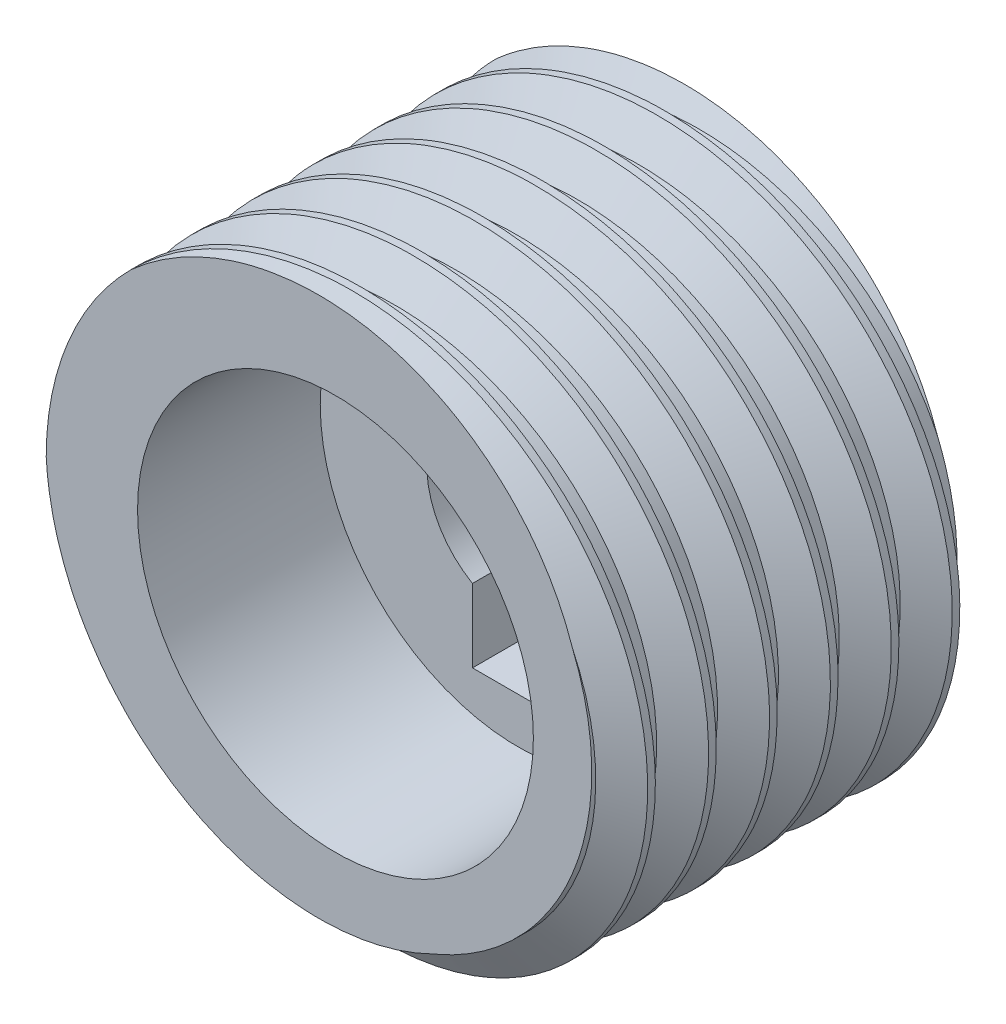
SolidWorks part; units mm, degrees
ref_plane "Front Plane" through (0, 0, 0) normal (0, 0, 1) x (1, 0, 0)
ref_plane "Top Plane" through (0, 0, 0) normal (0, 1, 0) x (1, 0, 0)
ref_plane "Right Plane" through (0, 0, 0) normal (1, 0, 0) x (0, 0, -1)
sketch "Sketch2" plane through (0, 0, 0) normal (0, 0, 1) x (1, 0, 0)
  circle A0 centre (0, 0) radius 4.75
  dimension "D1" = 9.5
extrude "Boss-Extrude1" add sketch "Sketch2" against normal blind 6
sketch "Sketch5" plane through (0, 0, 0) normal (0, 0, 1) x (1, 0, 0)
  circle A0 centre (0, 0) radius 3.25
  dimension "D1" = 6.5
extrude "Cut-Extrude1" cut sketch "Sketch5" against normal blind 3
thread "Thread1" pitch 1 method cut trim with start face yes profile "Thread Profile1" start angle 0, offset 1, length 0, pitch 1, diameter 9.5
ref_plane "Plane1" through (-4.75, 0, 1) normal (0, -1, 0) x (-1, 0, 0)
sketch "Thread Profile1" plane through (-4.75, 0, 1) normal (0, -1, 0) x (-1, 0, 0)
  line L0 (0, 0) -> (0, 1) construction
  line L11 (0, 0) -> (0, 0.875)
  line L12 (0, 0.875) -> (-0.5413, 0.5625)
  line L13 (-0.5413, 0.5625) -> (-0.5413, 0.3125)
  line L15 (-0.5413, 0.3125) -> (0, 0)
  line L17 (-0.5413, 0.4375) -> (0, 0.4375) construction
  point P2 (0, 0)
  dimension "Pitch" = 1
  dimension "Profile_Angle" = 60
  dimension "Profile_Land" = 0.25
  dimension "Profile_Height" = 0.5413
sketch "Sketch11" plane through (0, 0, -3) normal (0, 0, 1) x (1, 0, 0)
  line L1 (-0.75, 2.5) -> (0.75, 2.5)
  line L2 (-0.75, 2.5) -> (-0.75, -2.5)
  line L3 (-0.75, -2.5) -> (0.75, -2.5)
  line L4 (0.75, 2.5) -> (0.75, -2.5)
  line L5 (-0.75, 2.5) -> (0.75, -2.5) construction
  line L6 (-0.75, -2.5) -> (0.75, 2.5) construction
  point P0 (0, 0)
  dimension "D1" = 1.5
  dimension "D2" = 5
extrude "Cut-Extrude2" cut sketch "Sketch11" against normal blind 3
sketch "Sketch12" plane through (0, 0, -3) normal (0, 0, 1) x (1, 0, 0)
  circle A0 centre (0, 0) radius 1.5
  dimension "D1" = 3
extrude "Cut-Extrude3" cut sketch "Sketch12" against normal through all
